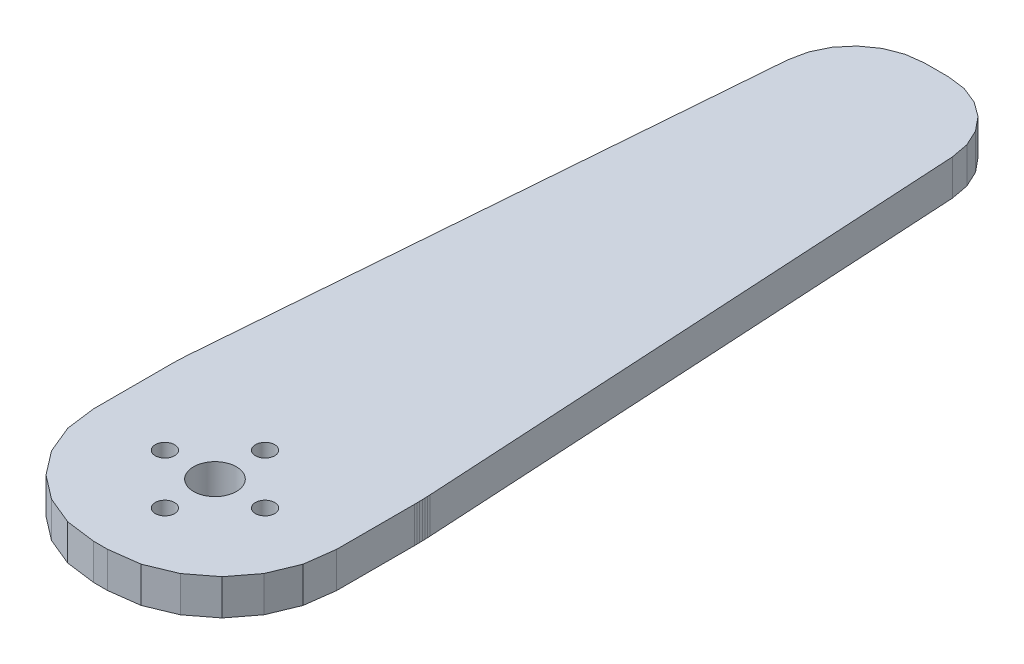
SolidWorks part; units mm, degrees
ref_plane "Front Plane" through (0, 0, 0) normal (0, 0, 1) x (1, 0, 0)
ref_plane "Top Plane" through (0, 0, 0) normal (0, 1, 0) x (1, 0, 0)
ref_plane "Right Plane" through (0, 0, 0) normal (1, 0, 0) x (0, 0, -1)
sketch "S_prism1" plane through (0, 0, 0) normal (0, 1, 0) x (1, 0, 0)
  line L0 (-17, 0) -> (-16.455, -4.141)
  line L1 (-16.455, -4.141) -> (-14.856, -8)
  line L2 (-14.856, -8) -> (-12.314, -11.314)
  line L3 (-12.314, -11.314) -> (-9, -13.856)
  line L4 (-9, -13.856) -> (-5.141, -15.455)
  line L5 (-5.141, -15.455) -> (-1, -16)
  line L6 (-1, -16) -> (1, -16)
  line L7 (1, -16) -> (5.141, -15.455)
  line L8 (5.141, -15.455) -> (9, -13.856)
  line L9 (9, -13.856) -> (12.314, -11.314)
  line L10 (12.314, -11.314) -> (14.856, -8)
  line L11 (14.856, -8) -> (16.455, -4.141)
  line L12 (16.455, -4.141) -> (17, 0)
  line L13 (17, 0) -> (17, 10.865)
  line L14 (17, 10.865) -> (16.998, 11.243)
  line L15 (16.998, 11.243) -> (16.993, 11.621)
  line L16 (16.993, 11.621) -> (16.984, 12)
  line L17 (16.984, 12) -> (16.971, 12.378)
  line L18 (16.971, 12.378) -> (16.955, 12.756)
  line L19 (16.955, 12.756) -> (16.936, 13.134)
  line L20 (16.936, 13.134) -> (12.536, 90.567)
  line L21 (12.536, 90.567) -> (12.078, 93.042)
  line L22 (12.078, 93.042) -> (11.017, 95.324)
  line L23 (11.017, 95.324) -> (9.42, 97.269)
  line L24 (9.42, 97.269) -> (7.387, 98.753)
  line L25 (7.387, 98.753) -> (5.049, 99.683)
  line L26 (5.049, 99.683) -> (2.552, 100)
  line L27 (2.552, 100) -> (-0.764, 100)
  line L28 (-0.764, 100) -> (-3.224, 99.693)
  line L29 (-3.224, 99.693) -> (-5.533, 98.79)
  line L30 (-5.533, 98.79) -> (-7.549, 97.346)
  line L31 (-7.549, 97.346) -> (-9.148, 95.451)
  line L32 (-9.148, 95.451) -> (-10.231, 93.221)
  line L33 (-10.231, 93.221) -> (-10.732, 90.793)
  line L34 (-10.732, 90.793) -> (-16.874, 13.583)
  line L35 (-16.874, 13.583) -> (-16.913, 13.056)
  line L36 (-16.913, 13.056) -> (-16.944, 12.527)
  line L37 (-16.944, 12.527) -> (-16.968, 11.999)
  line L38 (-16.968, 11.999) -> (-16.986, 11.47)
  line L39 (-16.986, 11.47) -> (-16.996, 10.941)
  line L40 (-16.996, 10.941) -> (-17, 10.412)
  line L41 (-17, 10.412) -> (-17, 0)
  dimension "P1" = 17
  dimension "P2" = 16.455
  dimension "P3" = 4.141
  dimension "P4" = 14.856
  dimension "P5" = 8
  dimension "P6" = 12.314
  dimension "P7" = 11.314
  dimension "P8" = 9
  dimension "P9" = 13.856
  dimension "P10" = 5.141
  dimension "P11" = 15.455
  dimension "P12" = 1
  dimension "P13" = 16
  dimension "P14" = 1
  dimension "P15" = 16
  dimension "P16" = 5.141
  dimension "P17" = 15.455
  dimension "P18" = 9
  dimension "P19" = 13.856
  dimension "P20" = 12.314
  dimension "P21" = 11.314
  dimension "P22" = 14.856
  dimension "P23" = 8
  dimension "P24" = 16.455
  dimension "P25" = 4.141
  dimension "P26" = 17
  dimension "P27" = 17
  dimension "P28" = 10.865
  dimension "P29" = 16.998
  dimension "P30" = 11.243
  dimension "P31" = 16.993
  dimension "P32" = 11.621
  dimension "P33" = 16.984
  dimension "P34" = 12
  dimension "P35" = 16.971
  dimension "P36" = 12.378
  dimension "P37" = 16.955
  dimension "P38" = 12.756
  dimension "P39" = 16.936
  dimension "P40" = 13.134
  dimension "P41" = 12.536
  dimension "P42" = 90.567
  dimension "P43" = 12.078
  dimension "P44" = 93.042
  dimension "P45" = 11.017
  dimension "P46" = 95.324
  dimension "P47" = 9.42
  dimension "P48" = 97.269
  dimension "P49" = 7.387
  dimension "P50" = 98.753
  dimension "P51" = 5.049
  dimension "P52" = 99.683
  dimension "P53" = 2.552
  dimension "P54" = 100
  dimension "P55" = 0.764
  dimension "P56" = 100
  dimension "P57" = 3.224
  dimension "P58" = 99.693
  dimension "P59" = 5.533
  dimension "P60" = 98.79
  dimension "P61" = 7.549
  dimension "P62" = 97.346
  dimension "P63" = 9.148
  dimension "P64" = 95.451
  dimension "P65" = 10.231
  dimension "P66" = 93.221
  dimension "P67" = 10.732
  dimension "P68" = 90.793
  dimension "P69" = 16.874
  dimension "P70" = 13.583
  dimension "P71" = 16.913
  dimension "P72" = 13.056
  dimension "P73" = 16.944
  dimension "P74" = 12.527
  dimension "P75" = 16.968
  dimension "P76" = 11.999
  dimension "P77" = 16.986
  dimension "P78" = 11.47
  dimension "P79" = 16.996
  dimension "P80" = 10.941
  dimension "P81" = 17
  dimension "P82" = 10.412
extrude "Boss_1" add sketch "S_prism1" along normal blind 5
ref_plane "PY_m0_100" through (0, -0.1, 0) normal (0, 1, 0) x (1, 0, 0)
sketch "S_hole2" plane through (0, -0.1, 0) normal (0, 1, 0) x (1, 0, 0)
  circle A0 centre (0, 0) radius 3
  dimension "D1_S_hole2" = 6
extrude "Hole_2" cut sketch "S_hole2" along normal blind 5.2
sketch "S_hole3" plane through (0, -0.1, 0) normal (0, 1, 0) x (1, 0, 0)
  circle A0 centre (7, 0) radius 1.35
  dimension "D1_S_hole3" = 2.7
  dimension "P2" = 7
extrude "Hole_3" cut sketch "S_hole3" along normal blind 5.2
sketch "S_hole4" plane through (0, -0.1, 0) normal (0, 1, 0) x (1, 0, 0)
  circle A0 centre (0, -7) radius 1.35
  dimension "D1_S_hole4" = 2.7
  dimension "P2" = 7
extrude "Hole_4" cut sketch "S_hole4" along normal blind 5.2
sketch "S_hole5" plane through (0, -0.1, 0) normal (0, 1, 0) x (1, 0, 0)
  circle A0 centre (-7, 0) radius 1.35
  dimension "D1_S_hole5" = 2.7
  dimension "P2" = 7
extrude "Hole_5" cut sketch "S_hole5" along normal blind 5.2
sketch "S_hole6" plane through (0, -0.1, 0) normal (0, 1, 0) x (1, 0, 0)
  circle A0 centre (0, 7) radius 1.35
  dimension "D1_S_hole6" = 2.7
  dimension "P2" = 7
extrude "Hole_6" cut sketch "S_hole6" along normal blind 5.2
equation "\"plate_t\" = 3"
equation "\"clearance\" = 0.4"
